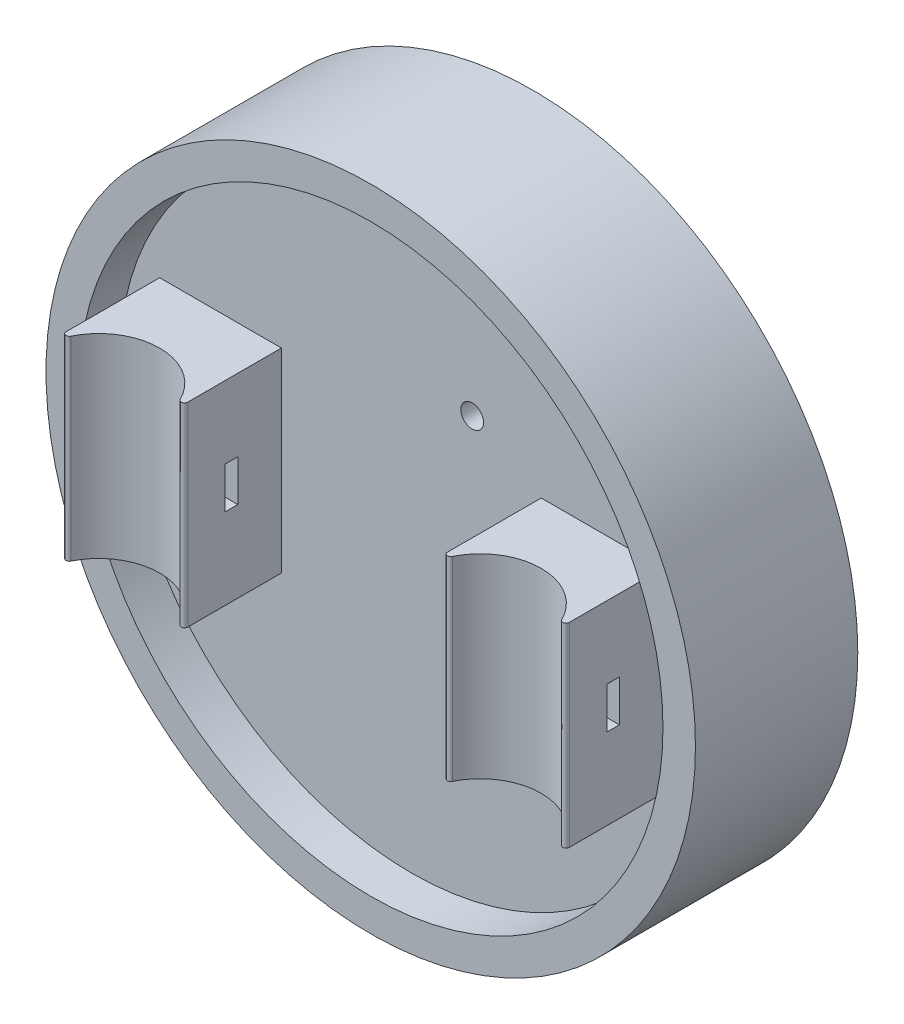
SolidWorks part; units mm, degrees
ref_plane "정면" through (0, 0, 0) normal (0, 0, 1) x (1, 0, 0)
ref_plane "윗면" through (0, 0, 0) normal (0, 1, 0) x (1, 0, 0)
ref_plane "우측면" through (0, 0, 0) normal (1, 0, 0) x (0, 0, -1)
sketch "스케치1" plane through (0, 0, 0) normal (0, 0, 1) x (1, 0, 0)
  line L5 (31.7937, -12) -> (-31.7937, 12) construction
  line L6 (31.7937, 12) -> (-31.7937, -12) construction
  line L7 (-31, 12) -> (-16, 12)
  line L8 (-31, 12) -> (-31, -12)
  line L9 (-31, -12) -> (-16, -12)
  line L10 (-16, 12) -> (-16, -12)
  line L11 (16, 12) -> (31, 12)
  line L12 (16, 12) -> (16, -12)
  line L13 (16, -12) -> (31, -12)
  line L14 (31, 12) -> (31, -12)
  circle A2 centre (0, 0) radius 40
  circle A3 centre (0, 0) radius 36
  dimension "D1" = 15
  dimension "D2" = 15
  dimension "D3" = 32
extrude "보스-돌출4" add sketch "스케치1" against normal blind 15 contours A2
extrude "보스-돌출5" add sketch "스케치1<8>" along normal blind 15 contours L10 L7 L8 L9 | L14 L11 L12 L13 region at (-23.5, 0, 0) region at (23.5, 0, 0)
sketch "스케치1<8>" plane through (0, 0, 0) normal (0, 0, 1) x (1, 0, 0) same geometry as "스케치1"
extrude "보스-돌출6" add sketch "스케치1<9>" along normal blind 5 contours A2 A3 region at (-38.8686, 0, 0)
sketch "스케치1<9>" plane through (0, 0, 0) normal (0, 0, 1) x (1, 0, 0) same geometry as "스케치1"
sketch "스케치2" plane through (0, -12, 0) normal (0, -1, 0) x (1, 0, 0)
  line L0 (-31, 15) -> (-16, 15) construction
  line L1 (16, 15) -> (31, 15) construction
  circle A0 centre (-23.5, 15) radius 7.5
  circle A1 centre (23.5, 15) radius 7.5
extrude "컷-돌출1" cut sketch "스케치2" against normal through all both and the other way through all
fillet "필렛1" radius 0.4 4 edges at (31, 0, 15) (16, 0, 15) (-16, 0, 15) (-31, 0, 15)
sketch "스케치3" plane through (31, 0, 0) normal (1, 0, 0) x (0, 0, -1)
  line L1 (-6.9226, 3.091) -> (-5.3745, 3.091)
  line L2 (-6.9226, 3.091) -> (-6.9226, -2.0091)
  line L3 (-6.9226, -2.0091) -> (-5.3745, -2.0091)
  line L4 (-5.3745, 3.091) -> (-5.3745, -2.0091)
  line L5 (-6.9226, 3.091) -> (-5.3745, -2.0091) construction
  line L6 (-6.9226, -2.0091) -> (-5.3745, 3.091) construction
  point P0 (-6.1486, 0.5409)
extrude "컷-돌출2" cut sketch "스케치3" against normal through all both and the other way through all
sketch "스케치4" plane through (0, 0, 0) normal (0, 0, 1) x (1, 0, 0)
  line L0 (-23.5, 12) -> (23.5, 12)
  line L1 (-16.7595, 12) -> (-30.2405, 12) construction
  line L2 (30.2405, 12) -> (16.7595, 12) construction
  line L3 (0, 12) -> (0, -14.993)
  line L4 (0, -14.993) -> (6, -14.993)
  line L5 (6, -14.993) -> (6, -2.4916)
  line L6 (16.7595, -12) -> (30.2405, -12) construction
  circle A0 centre (7.5, -15) radius 1.5
  circle A1 centre (7.5, 15) radius 1.5
  dimension "D2" = 3
  dimension "D5" = 3
  dimension "D1" = 6
  dimension "D3" = 1.5
  dimension "D4" = 3
extrude "컷-돌출3" cut sketch "스케치4" against normal blind 5 contours A1 | A0 region at (7.5, -15, 0) region at (7.5, 15, 0)
sketch "스케치5" plane through (0, 0, 0) normal (0, 0, 1) x (1, 0, 0)
  line L0 (7.5, 15) -> (7.5, -15)
  line L1 (7.5, 0) -> (7.5, -16.5)
  line L2 (7.5, 0) -> (7.5, 16.5)
  circle A0 centre (7.5, 15) radius 1.5 construction
  circle A1 centre (7.5, 16.5) radius 1.4
  circle A2 centre (7.5, -16.5) radius 1.4
  circle M1 centre (7.5, 15) radius 1.5
  circle M2 centre (7.5, -15) radius 1.5
extrude "보스-돌출8" add sketch "스케치5" against normal blind 5 contours A1 L0 L2 M1 | A1 L2 M1 | L2 A1 M1 | A1 L2 L0 M1 | A2 L0 L1 M2 | A2 L1 L0 M2 | L1 A2 M2 | A2 L1 M2 region at (8.2176, 14.5715, 0) region at (6.7824, 14.5715, 0) region at (8.2176, -14.5715, 0) region at (6.7824, -14.5715, 0) region at (7.0156, 15.8055, 0) region at (7.9844, 15.8055, 0) region at (7.0156, -15.8055, 0) region at (7.9844, -15.8055, 0)
extrude "컷-돌출4" cut sketch "스케치5<4>" against normal blind 5 contours A1 M1 | A1 L2 M1 | L2 A1 M1 | L1 A2 M2 | A2 L1 M2 | A2 M2 region at (7.0156, 15.8055, 0) region at (7.9844, 15.8055, 0) region at (7.5, 16.9604, 0) region at (7.5, -16.9604, 0) region at (7.0156, -15.8055, 0) region at (7.9844, -15.8055, 0)
sketch "스케치5<4>" plane through (0, 0, 0) normal (0, 0, 1) x (1, 0, 0) same geometry as "스케치5"
